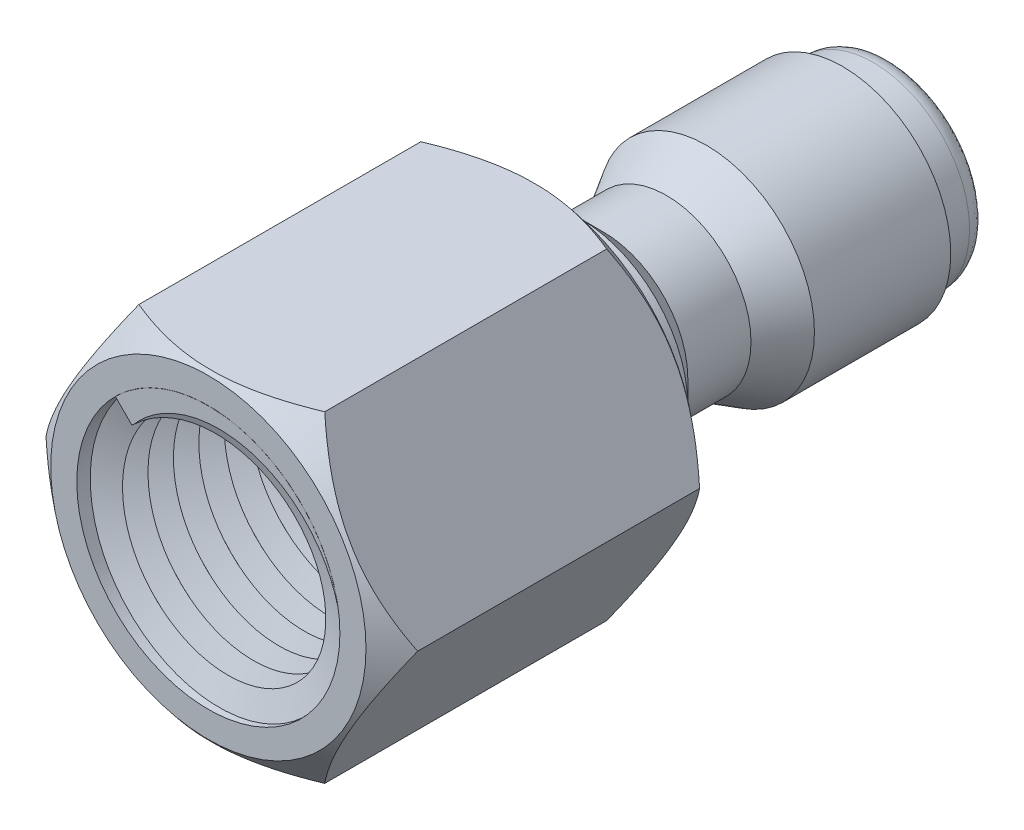
SolidWorks part; units mm, degrees
material "AISI 304"
ref_plane "Front Plane" through (0, 0, 0) normal (0, 0, 1) x (1, 0, 0)
ref_plane "Top Plane" through (0, 0, 0) normal (0, 1, 0) x (1, 0, 0)
ref_plane "Right Plane" through (0, 0, 0) normal (1, 0, 0) x (0, 0, -1)
sketch "Sketch1" plane through (0, 0, 0) normal (0, 0, 1) x (1, 0, 0)
  line L1 (10.0453, 0) -> (5.0227, 8.6995)
  line L2 (5.0227, 8.6995) -> (-5.0227, 8.6995)
  line L3 (-5.0227, 8.6995) -> (-10.0453, 0)
  line L4 (-10.0453, 0) -> (-5.0227, -8.6995)
  line L5 (-5.0227, -8.6995) -> (5.0227, -8.6995)
  line L6 (5.0227, -8.6995) -> (10.0453, 0)
  circle A0 centre (0, 0) radius 8.6995 construction
  dimension "D1" = 17.399
extrude "Boss-Extrude1" add sketch "Sketch1" along normal blind 17.78
sketch "Sketch2" plane through (0, 0, 0) normal (0, 0, 1) x (1, 0, 0)
  circle A0 centre (0, 0) radius 5.842
  dimension "D1" = 11.684
extrude "Boss-Extrude2" add sketch "Sketch2" against normal blind 19.05
sketch "Sketch4" plane through (0, 0, -19.05) normal (0, 0, -1) x (-1, 0, 0)
  circle A0 centre (0, 0) radius 3.175
  dimension "D1" = 6.35
extrude "Cut-Extrude1" cut sketch "Sketch4" against normal through all
sketch "Sketch6" plane through (0, 0, 17.78) normal (0, 0, 1) x (1, 0, 0)
  circle A0 centre (0, 0) radius 7.112
  dimension "D1" = 14.224
extrude "Cut-Extrude2" cut sketch "Sketch6" against normal blind 16.51
chamfer "Chamfer2" distance 2.286 angle 45 1 edges at (3.175, 0, 1.27)
sketch "Sketch7" plane through (0, 0, 17.78) normal (0, 0, 1) x (1, 0, 0)
  circle A0 centre (0, 0) radius 7.112
curve "Helix/Spiral1" pitch 1.3758 height 16.51 radius 7.112 centre (0, 0, 17.78) axis (0, 0, -1) start towards (-0.7071, 0.7071, 0)
ref_plane "Plane1" through (-5.0289, 5.0289, 17.78) normal (0.7068, 0.7068, -0.0308) x (0.7074, -0.706, 0.0335)
sketch "Sketch8" plane through (-5.0289, 5.0289, 17.78) normal (0.7068, 0.7068, -0.0308) x (0.7074, -0.706, 0.0335)
  line L0 (0.0077, -0.004) -> (-0.0849, 2.7532) construction
  line L1 (-0.0849, 2.7532) -> (0.0824, -2.2295) construction
  line L2 (-2.5869, -0.1669) -> (-3.1831, 17.5947) construction
  line L3 (-0.0083, 0.4713) -> (1.2769, 0.0386)
  line L4 (1.2769, 0.0386) -> (0.0236, -0.4793)
  line L5 (0.0236, -0.4793) -> (-0.0083, 0.4713)
  line L6 (1.2769, 0.0386) -> (0.0077, -0.004) construction
  dimension "D1" = 1.27
sweep "Sweep1" add profiles "Sketch8" path "Helix/Spiral1"
sketch "Sketch3" plane through (0, 0, 0) normal (0, 1, 0) x (1, 0, 0)
  line L0 (5.842, 2.2953) -> (4.572, 3.5653)
  line L1 (5.207, 16.891) -> (5.207, 19.05)
  line L2 (5.842, 19.05) -> (-5.842, 19.05) construction
  line L3 (5.207, 19.05) -> (5.207, 21.8079)
  line L4 (5.207, 21.8079) -> (6.7709, 21.8079)
  line L5 (6.7709, 21.8079) -> (6.7709, 16.1119)
  line L6 (6.7709, 16.1119) -> (5.842, 16.51)
  line L7 (5.842, 0) -> (5.842, 19.05) construction
  line L8 (5.842, 16.51) -> (5.207, 16.891)
  line L9 (4.572, 3.5653) -> (4.572, 6.9821)
  line L10 (4.572, 6.9821) -> (5.842, 9.1411)
  line L11 (5.842, 9.1411) -> (7.0241, 9.1411)
  line L12 (7.0241, 9.1411) -> (7.0241, 2.2953)
  line L13 (7.0241, 2.2953) -> (5.842, 2.2953)
  line L14 (8.5213, 0) -> (10.0453, -1.27)
  line L15 (10.0453, 0) -> (5.0227, 0) construction
  line L16 (10.0453, -17.78) -> (10.0453, 0) construction
  line L17 (10.0453, -1.27) -> (11.0901, -1.27)
  line L18 (11.0901, -1.27) -> (11.0901, 0.9299)
  line L19 (11.0901, 0.9299) -> (8.5213, 0.9299)
  line L20 (8.5213, 0.9299) -> (8.5213, 0)
  line L21 (10.0453, -16.51) -> (8.5213, -17.78)
  line L22 (10.0453, -17.78) -> (5.0227, -17.78) construction
  line L24 (8.5213, -18.5383) -> (10.5973, -18.5383)
  line L25 (10.5973, -18.5383) -> (10.5973, -16.51)
  line L26 (10.5973, -16.51) -> (10.0453, -16.51)
  line L27 (0, 0) -> (0, 25.9281) construction
  line L33 (8.5213, -17.78) -> (2.977, -17.78)
  line L35 (8.5213, -18.5383) -> (2.977, -18.5383)
  line L36 (2.977, -17.78) -> (2.977, -18.5383)
  dimension "D1" = 2.54
  dimension "D2" = 0.635
  dimension "D3" = 0.381
  dimension "D4" = 1.27
  dimension "D5" = 2.159
  dimension "D6" = 1.27
  dimension "D7" = 1.27
  dimension "D8" = 1.524
  dimension "D9" = 1.524
  dimension "D10" = 1.27
revolve "Cut-Revolve1" cut sketch "Sketch3" angle 360 about L27
fillet "Fillet2" radius 0.889 1 edges at (5.207, 0, -19.05) second distance 0.635 first distance on face at (5.207, 0, -16.891)
